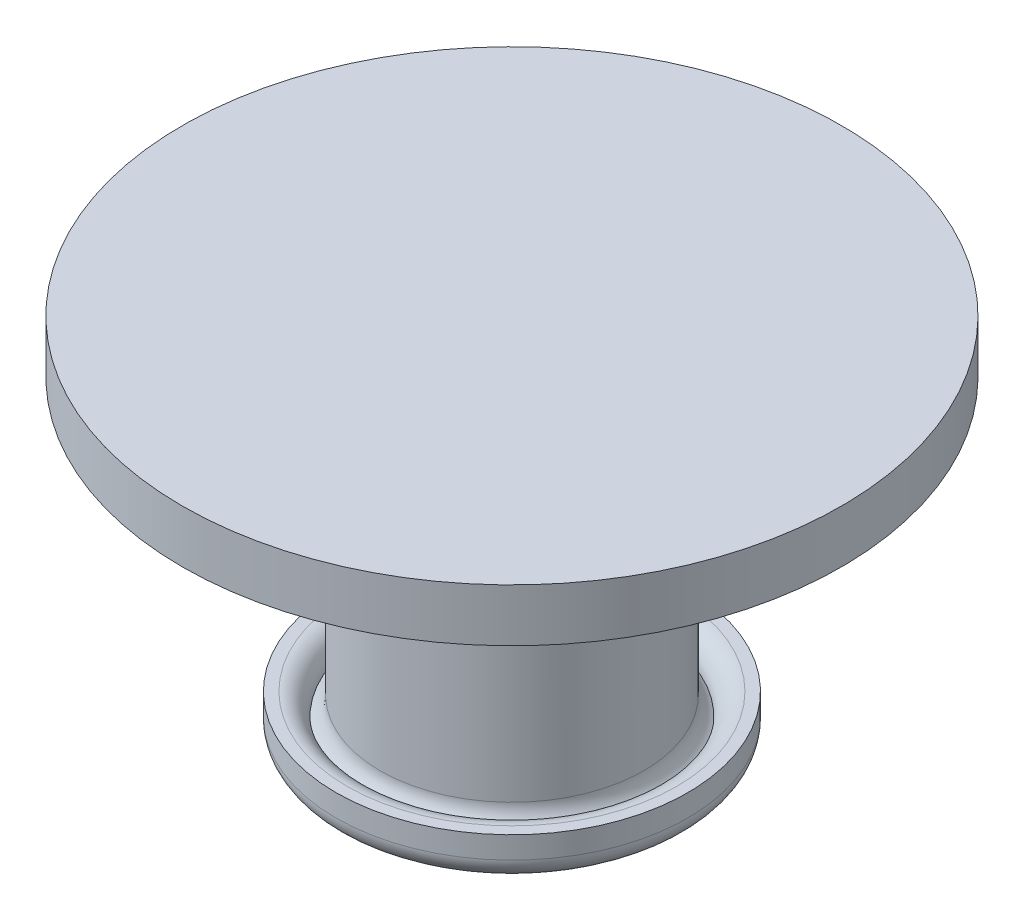
SolidWorks part; units mm, degrees
ref_plane "Plano frontal" through (0, 0, 0) normal (0, 0, 1) x (1, 0, 0)
ref_plane "Plano superior" through (0, 0, 0) normal (0, 1, 0) x (1, 0, 0)
ref_plane "Plano direito" through (0, 0, 0) normal (1, 0, 0) x (0, 0, -1)
sketch "Esboço1" plane through (0, 0, 0) normal (0, 1, 0) x (1, 0, 0)
  circle A0 centre (0, 0) radius 7.5
  dimension "D1" = 15
extrude "Ressalto-extrusão1" add sketch "Esboço1" along normal blind 1.2
sketch "Esboço2" plane through (0, 0, 0) normal (0, -1, 0) x (1, 0, 0)
  circle A0 centre (0, 0) radius 3
  dimension "D1" = 6
extrude "Ressalto-extrusão2" add sketch "Esboço2" along normal blind 7.2
sketch "Esboço3" plane through (0, -7.2, 0) normal (0, -1, 0) x (1, 0, 0)
  circle A0 centre (0, 0) radius 4
  dimension "D1" = 8
extrude "Ressalto-extrusão3" add sketch "Esboço3" against normal blind 1
sketch "Esboço4" plane through (0, -6.2, 0) normal (0, 1, 0) x (1, 0, 0)
  circle A0 centre (0, 0) radius 3.25
  circle A1 centre (0, 0) radius 3 construction
  circle A2 centre (0, 0) radius 3
  dimension "D1" = 6.5
extrude "Corte-extrusão1" cut sketch "Esboço4" against normal blind 0.5
sketch "Esboço5" plane through (0, -7.2, 0) normal (0, -1, 0) x (1, 0, 0)
  circle A0 centre (0, 0) radius 2.5
  dimension "D1" = 5
extrude "Corte-extrusão4" cut sketch "Esboço5" against normal blind 1
fillet "Filete1" radius 0.5 5 edges at (0, -6.7, 3) (0, -7.2, -4) (0, -6.2, 3.25) (0, -6.2, -2.5) (0, -7.2, -2.5)
